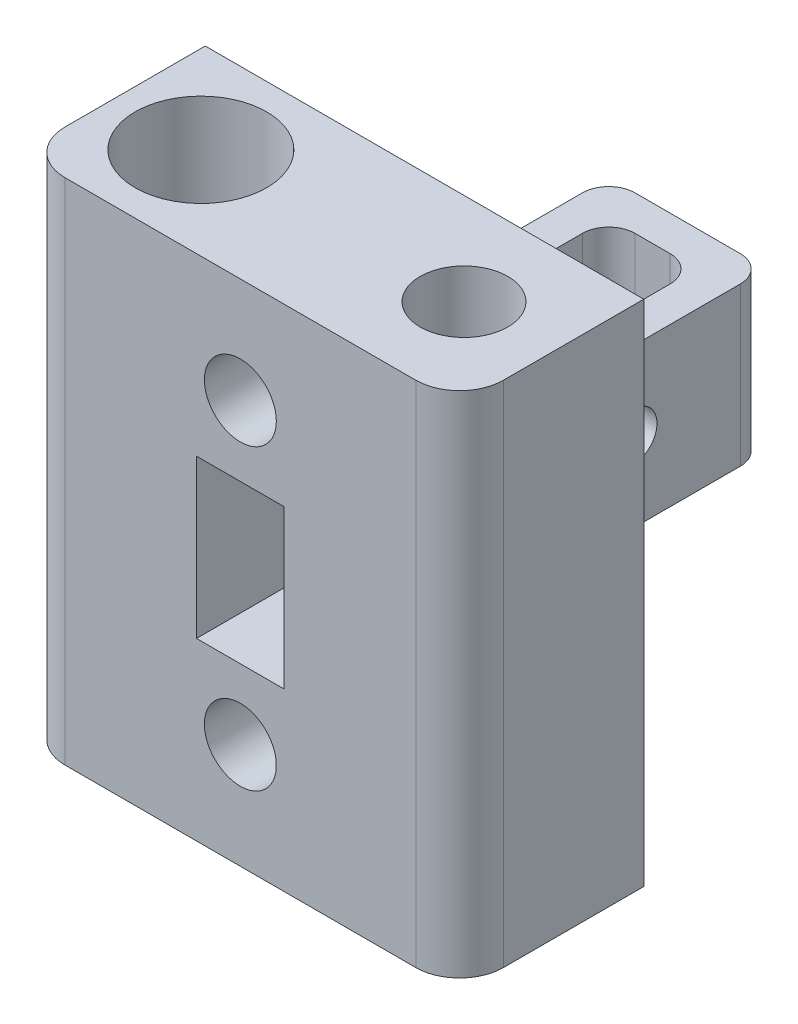
SolidWorks part; units mm, degrees
ref_plane "Front Plane" through (0, 0, 0) normal (0, 0, 1) x (1, 0, 0)
ref_plane "Top Plane" through (0, 0, 0) normal (0, 1, 0) x (1, 0, 0)
ref_plane "Right Plane" through (0, 0, 0) normal (1, 0, 0) x (0, 0, -1)
sketch "Sketch1" plane through (0, 0, 0) normal (0, 1, 0) x (1, 0, 0)
  line L1 (-25, 10.5) -> (25, 10.5)
  line L2 (-25, 10.5) -> (-25, -10.5)
  line L3 (-25, -10.5) -> (25, -10.5)
  line L4 (25, 10.5) -> (25, -10.5)
  line L5 (-25, 10.5) -> (25, -10.5) construction
  line L6 (-25, -10.5) -> (25, 10.5) construction
  point P0 (0, 0)
  dimension "D1" = 21
  dimension "D2" = 50
extrude "Boss-Extrude1" add sketch "Sketch1" along normal blind 58
sketch "Sketch3" plane through (0, 58, 0) normal (0, 1, 0) x (1, 0, 0)
  line L0 (-15, 0) -> (15, 0) construction
  circle A0 centre (-15, 0) radius 7.5
  dimension "D1" = 15
  dimension "D2" = 30
extrude "Cut-Extrude1" cut sketch "Sketch3" against normal blind 24 contours A0
sketch "Sketch4" plane through (0, 58, 0) normal (0, 1, 0) x (1, 0, 0)
  line L0 (-15, 0) -> (15, 0) construction
  circle A0 centre (15, 0) radius 5
  dimension "D1" = 10
extrude "Cut-Extrude2" cut sketch "Sketch4" against normal up to next
sketch "Sketch5" plane through (0, 0, 0) normal (0, -1, 0) x (1, 0, 0)
  circle A1 centre (-15, 0) radius 7.5
  circle A2 centre (-15, 0) radius 7.5
  dimension "D1" = 0
extrude "Cut-Extrude3" cut sketch "Sketch5" against normal blind 24
sketch "Sketch6" plane through (0, 0, 0) normal (0, -1, 0) x (1, 0, 0)
  circle A0 centre (-15, 0) radius 4.5
extrude "Cut-Extrude4" cut sketch "Sketch6" against normal up to next
sketch "Sketch7" plane through (0, 0, 10.5) normal (0, 0, 1) x (1, 0, 0)
  line L0 (0, 58) -> (0, 0) construction
  line L1 (-25, 58) -> (25, 58) construction
  line L2 (-25, 0) -> (25, 0) construction
  line L3 (-25, 29) -> (25, 29) construction
  line L4 (-25, 58) -> (-25, 0) construction
  line L5 (25, 58) -> (25, 0) construction
  circle A1 centre (0, 46) radius 4.1
  circle A2 centre (0, 12) radius 4.1
  point P24 (0, 12)
  dimension "D1" = 8.2
  dimension "D2" = 12
sketch "Sketch8" plane through (0, 0, 10.5) normal (0, 0, 1) x (1, 0, 0)
  line L0 (-25, 29) -> (25, 29) construction
  line L1 (-25, 58) -> (-25, 0) construction
  line L2 (25, 58) -> (25, 0) construction
  line L3 (0, 58) -> (0, 0) construction
  line L4 (-25, 58) -> (25, 58) construction
  line L6 (-5, 20) -> (5, 20)
  line L7 (-5, 20) -> (-5, 38)
  line L8 (-5, 38) -> (5, 38)
  line L9 (5, 20) -> (5, 38)
  line L10 (-5, 20) -> (5, 38) construction
  line L11 (-5, 38) -> (5, 20) construction
  point P11 (0, 29)
  dimension "D1" = 18
  dimension "D2" = 10
extrude "Cut-Extrude5" cut sketch "Sketch8" against normal up to next
sketch "Sketch10" plane through (0, 0, -10.5) normal (0, 0, -1) x (-1, 0, 0)
  line L0 (-25, 29) -> (25, 29) construction
  line L1 (-25, 58) -> (-25, 0) construction
  line L2 (25, 58) -> (25, 0) construction
  line L3 (0, 58) -> (0, 0) construction
  line L4 (-25, 58) -> (25, 58) construction
extrude "Cut-Extrude6" cut sketch "Sketch7" against normal blind 15
sketch "Sketch11" plane through (0, 0, -10.5) normal (0, 0, -1) x (-1, 0, 0)
  line L0 (-25, 29) -> (25, 29) construction
  line L1 (9, 38) -> (5, 38)
  line L2 (9, 38) -> (9, 20)
  line L3 (9, 20) -> (5, 20)
  line L4 (5, 38) -> (5, 20)
  line L5 (9, 38) -> (5, 20) construction
  line L6 (9, 20) -> (5, 38) construction
  line L7 (0, 58) -> (0, 0) construction
  line L8 (0, 58) -> (0, 0)
  line L9 (-9, 20) -> (-5, 20)
  line L10 (-5, 38) -> (-5, 20)
  line L11 (-9, 38) -> (-5, 38)
  line L12 (-9, 38) -> (-9, 20)
  point P0 (7, 29)
  line M7 (-5, 20) -> (-5, 38)
  line M9 (5, 38) -> (5, 20)
  dimension "D1" = 5
  dimension "D2" = 4
  dimension "D3" = 18
extrude "Boss-Extrude2" add sketch "Sketch11" along normal blind 26 contours L1 L4 L3 L2 M9 | L11 L12 L9 L10 M7 region at (-7, 29, -10.5) region at (7, 29, -10.5)
sketch "Sketch12" plane through (0, 0, -36.5) normal (0, 0, -1) x (-1, 0, 0)
  line L1 (9, 20) -> (-9, 20)
  line L2 (9, 20) -> (9, 38)
  line L3 (9, 38) -> (-9, 38)
  line L4 (-9, 20) -> (-9, 38)
extrude "Boss-Extrude3" add sketch "Sketch12" along normal blind 4
sketch "Sketch13" plane through (9, 0, 0) normal (1, 0, 0) x (0, 0, -1)
  line L3 (10.5, 29) -> (40.5, 29) construction
  line L4 (10.5, 38) -> (10.5, 20) construction
  line L5 (40.5, 38) -> (40.5, 20) construction
  line L6 (16.25, 29) -> (25.25, 29) construction
  line L7 (16.25, 31.75) -> (25.25, 31.75)
  line L8 (16.25, 26.25) -> (25.25, 26.25)
  arc A0 (16.25, 31.75) -> (16.25, 26.25) centre (16.25, 29) ccw
  arc A1 (25.25, 26.25) -> (25.25, 31.75) centre (25.25, 29) ccw
  point P1 (13.5, 29)
  point P14 (20.75, 29)
  dimension "D1" = 5.5
  dimension "D2" = 3
  dimension "D3" = 9
extrude "Cut-Extrude7" cut sketch "Sketch13" against normal through all
fillet "Fillet1" radius 5 2 edges at (-25, 29, 10.5) (25, 29, 10.5)
fillet "Fillet2" radius 5 4 edges at (-7, 20, -10.5) (7, 20, -10.5) (-7, 38, -10.5) (7, 38, -10.5)
fillet "Fillet3" radius 3 4 edges at (-5, 29, -36.5) (5, 29, -36.5) (-9, 29, -40.5) (9, 29, -40.5)
